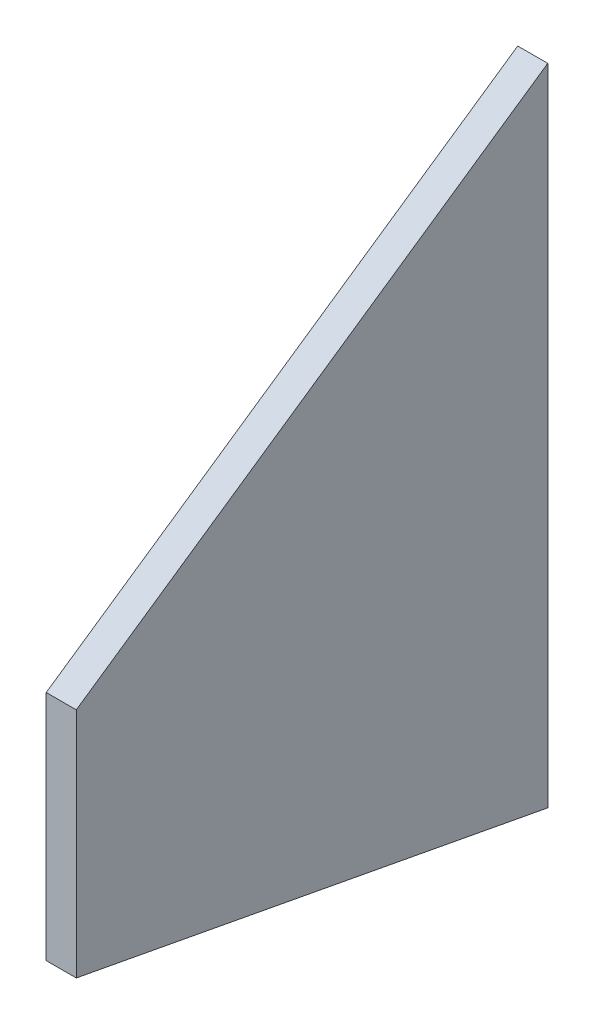
SolidWorks part; units mm, degrees
ref_plane "Front Plane" through (0, 0, 0) normal (0, 0, 1) x (1, 0, 0)
ref_plane "Top Plane" through (0, 0, 0) normal (0, 1, 0) x (1, 0, 0)
ref_plane "Right Plane" through (0, 0, 0) normal (1, 0, 0) x (0, 0, -1)
ref_plane "Plane3" through (0, 0, 127) normal (0, 0, 1) x (1, 0, 0)
ref_plane "Plane1" through (-63.5, 0, 0) normal (1, 0, 0) x (0, 0, -1)
ref_plane "Plane2" through (0, 149.86, 0) normal (0, 1, 0) x (1, 0, 0)
sketch "Sketch2" plane through (0, 0, 0) normal (0, 1, 0) x (1, 0, 0)
  line L0 (-57.15, 0) -> (224.536, 0)
  line L1 (224.536, 0) -> (-24.3577, -163.9616)
  line L2 (-24.3577, -163.9616) -> (-57.15, 0)
  line L3 (0, 0) -> (0, -127) construction
  line L4 (-31.75, -127) -> (31.75, -127) construction
  point P2 (0, 0)
  dimension "D1" = 281.686
  dimension "D2" = 57.15
  dimension "D3" = 63.5
  dimension "D4" = 127
extrude "Boss-Extrude1" add sketch "Sketch2" along normal blind 152.4
sketch "Sketch3" plane through (-63.5, 0, 0) normal (1, 0, 0) x (0, 0, -1)
  line L0 (0, 76.2) -> (-127, 76.2) construction
  line L1 (0, 152.4) -> (0, 0) construction
  line L2 (-127, 44.45) -> (-127, 107.95) construction
  line L3 (0, 152.4) -> (-127, 107.95)
  line L4 (0, 0) -> (-127, 44.45)
  line L5 (-127, 107.95) -> (-217.7143, 76.2)
  line L6 (-127, 44.45) -> (-217.7143, 76.2)
  line L7 (0, 152.4) -> (0, 0)
  point P7 (-127, 76.2)
  dimension "D1" = 127
  dimension "D2" = 63.5
extrude "Cut-Extrude2" cut sketch "Sketch3" along normal through all flip side to cut
shell "Shell1" thickness 6.35 removed face at (83.693, 76.2, 0)
sketch "Sketch8" plane through (0, 0, 127) normal (0, 0, 1) x (1, 0, 0)
  line L1 (-92.1964, -50.8668) -> (173.8662, -50.8668)
  line L2 (-92.1964, -50.8668) -> (-92.1964, 231.3249)
  line L3 (-92.1964, 231.3249) -> (173.8662, 231.3249)
  line L4 (173.8662, -50.8668) -> (173.8662, 231.3249)
extrude "Cut-Extrude6" cut sketch "Sketch8" along normal through all
sketch "Sketch4" plane through (-63.5, 0, 0) normal (1, 0, 0) x (0, 0, -1)
  line L1 (0, 152.4) -> (0, 145.6723)
  line L2 (0, 145.6723) -> (-163.9616, 88.2857)
  line L4 (-163.9616, 64.1143) -> (0, 6.7277)
  line L5 (0, 152.4) -> (-163.9616, 95.0134)
  line L7 (-163.9616, 57.3866) -> (0, 0)
  line L8 (-163.9616, 95.0134) -> (-163.9616, 57.3866) construction
  line L9 (-163.9616, 95.0134) -> (-163.9616, 88.2857)
  line L10 (-163.9616, 64.1143) -> (-163.9616, 57.3866)
  line L11 (0, 152.4) -> (0, 0) construction
  line L12 (0, 0) -> (0, 6.7277)
  line L13 (-127, 107.95) -> (0, 152.4) construction
  line L14 (-127, 44.45) -> (0, 0) construction
extrude "Cut-Extrude3" cut sketch "Sketch4" along normal through all
sketch "Sketch5" plane through (0, 149.86, 0) normal (0, 1, 0) x (1, 0, 0)
  line L0 (-19.6044, -155.349) -> (-18.6358, -160.1922)
  line L1 (31.75, -127) -> (224.536, 0) construction
  line L2 (-25.2742, -127) -> (-50.6742, 0) construction
  line L3 (-18.6358, -160.1922) -> (344.3171, -160.1922)
  line L4 (344.3171, -160.1922) -> (317.9032, 72.8661)
  line L5 (317.9032, 72.8661) -> (-35.1132, 43.3185)
  line L6 (-35.1132, 43.3185) -> (-19.6044, -155.349)
  point P2 (-18.6358, -155.1553)
extrude "Cut-Extrude4" cut sketch "Sketch5" against normal through all
